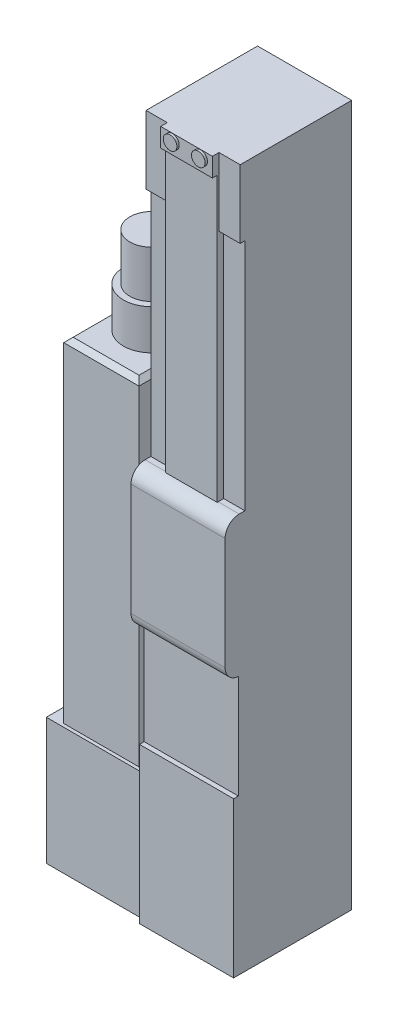
SolidWorks part; units mm, degrees
ref_plane "Front" through (0, 0, 0) normal (0, 0, 1) x (1, 0, 0)
ref_plane "Top" through (0, 0, 0) normal (0, 1, 0) x (1, 0, 0)
ref_plane "Right" through (0, 0, 0) normal (1, 0, 0) x (0, 0, -1)
sketch "Sketch1" plane through (0, 0, 0) normal (0, 0, 1) x (1, 0, 0)
  line L0 (0, 172.9723) -> (0, -36.0329) construction
  line L2 (10, 0) -> (-10, 0)
  line L3 (10, 0) -> (10, 149)
  line L4 (10, 149) -> (-10, 149)
  line L5 (-10, 0) -> (-10, 149)
  dimension "D1" = 149
  dimension "D2" = 20
extrude "Boss-Extrude1" add sketch "Sketch1" against normal blind 26.9
sketch "Sketch2" plane through (0, 0, 0) normal (0, -1, 0) x (1, 0, 0)
  line L0 (-10, -26.9) -> (-10, 0) construction
  line L1 (-31, -3) -> (-10, -3)
  line L2 (-31, -3) -> (-31, -20.5)
  line L3 (-31, -20.5) -> (-10, -20.5)
  line L4 (-10, -3) -> (-10, -20.5)
  line L6 (-10, 0) -> (10, 0) construction
  dimension "D1" = 3
  dimension "D2" = 17.5
  dimension "D3" = 31
extrude "Boss-Extrude2" add sketch "Sketch2" against normal blind 26.9
sketch "Sketch3" plane through (0, 26.9, 0) normal (0, 1, 0) x (1, 0, 0)
  line L1 (-28, 22.6) -> (-12, 22.6)
  line L2 (-28, 22.6) -> (-28, 3.7)
  line L3 (-28, 3.7) -> (-12, 3.7)
  line L4 (-12, 22.6) -> (-12, 3.7)
  line L5 (10, 0) -> (-10, 0) construction
  dimension "D1" = 18.9
  dimension "D2" = 3.7
  dimension "D3" = 12
  dimension "D4" = 16
extrude "Boss-Extrude3" add sketch "Sketch3" along normal blind 71.1
sketch "Sketch4" plane through (0, 98, 0) normal (0, 1, 0) x (1, 0, 0)
  line L1 (10, 0) -> (-10, 0) construction
  circle A0 centre (-20, 14.4) radius 6
  dimension "D1" = 12
  dimension "D2" = 14.4
  dimension "D3" = 20
extrude "Boss-Extrude4" add sketch "Sketch4" along normal blind 8.5
sketch "Sketch5" plane through (0, 106.5, 0) normal (0, 1, 0) x (1, 0, 0)
  circle A0 centre (-20, 14.4) radius 4.65
  dimension "D1" = 9.3
extrude "Boss-Extrude5" add sketch "Sketch5" along normal blind 10
sketch "Sketch7" plane through (0, 0, 0) normal (0, 0, 1) x (1, 0, 0)
  line L4 (10, 0) -> (10, 149)
  line L5 (10, 149) -> (-10, 149)
  line L6 (-10, 149) -> (-10, 0)
  line L7 (-10, 0) -> (10, 0)
  line L8 (10, 0) -> (10, 149)
  line L9 (10, 149) -> (-10, 149)
  line L10 (-10, 149) -> (-10, 0)
  line L11 (-10, 0) -> (10, 0)
  dimension "D1" = 0
extrude "Cut-Extrude1" cut sketch "Sketch7" against normal blind 2.8
sketch "Sketch8" plane through (0, 0, -2.8) normal (0, 0, 1) x (1, 0, 0)
  line L1 (-10, 149) -> (-5.5, 149)
  line L2 (-10, 149) -> (-10, 55)
  line L3 (-10, 55) -> (-5.5, 55)
  line L4 (-5.5, 149) -> (-5.5, 55)
  line L5 (-10, 0) -> (10, 0) construction
  line L6 (10, 149) -> (5.5, 149)
  line L7 (10, 149) -> (10, 55)
  line L8 (10, 55) -> (5.5, 55)
  line L9 (5.5, 149) -> (5.5, 55)
  dimension "D1" = 55
  dimension "D2" = 4.5
extrude "Cut-Extrude2" cut sketch "Sketch8" against normal blind 1.4
sketch "Sketch17" plane through (0, 0, -26.9) normal (0, 0, -1) x (-1, 0, 0)
  line L0 (0, 165.2015) -> (0, -12.9133) construction
  line L1 (0, 120) -> (0, 119) construction
  line L2 (1.5, 120) -> (1.5, 119)
  line L3 (-1.5, 120) -> (-1.5, 119)
  line L4 (10, 0) -> (-10, 0) construction
  arc A0 (1.5, 120) -> (-1.5, 120) centre (0, 120) ccw
  arc A1 (-1.5, 119) -> (1.5, 119) centre (0, 119) ccw
  circle A2 centre (0, 69.5) radius 1.5
  point P5 (0, 119.5)
  dimension "D3" = 3
  dimension "D1" = 1
  dimension "D2" = 3
  dimension "D4" = 69.5
  dimension "D5" = 50
extrude "Cut-Extrude3" cut sketch "Sketch17" against normal blind 3
sketch "Sketch9" plane through (0, 0, -4.2) normal (0, 0, 1) x (1, 0, 0)
  line L0 (10, 55) -> (10, 149) construction
  line L1 (-10, 55) -> (10, 55)
  line L2 (-10, 55) -> (-10, 84.8)
  line L3 (-10, 84.8) -> (10, 84.8)
  line L4 (10, 55) -> (10, 84.8)
  dimension "D1" = 29.8
extrude "Boss-Extrude6" add sketch "Sketch9" along normal blind 4.2
sketch "Sketch12" plane through (0, 0, -2.8) normal (0, 0, 1) x (1, 0, 0)
  line L0 (-10, 55) -> (-10, 0) construction
  line L1 (10, 0) -> (-10, 0)
  line L2 (10, 0) -> (10, 33)
  line L3 (10, 33) -> (-10, 33)
  line L4 (-10, 0) -> (-10, 33)
  dimension "D1" = 33
extrude "Boss-Extrude7" add sketch "Sketch12" along normal blind 1
sketch "Sketch14" plane through (0, 0, -2.8) normal (0, 0, 1) x (1, 0, 0)
  line L0 (5.5, 149) -> (5.5, 84.8) construction
  line L1 (-5.5, 149) -> (5.5, 149)
  line L2 (-5.5, 149) -> (-5.5, 145)
  line L3 (-5.5, 145) -> (5.5, 145)
  line L4 (5.5, 149) -> (5.5, 145)
  dimension "D1" = 4
extrude "Boss-Extrude8" add sketch "Sketch14" along normal blind 1
sketch "Sketch15" plane through (0, 0, -1.8) normal (0, 0, 1) x (1, 0, 0)
  line L0 (-10, 0) -> (10, 0) construction
  line L1 (0, 159.5543) -> (0, -7.81) construction
  circle A0 centre (-3, 147.5) radius 1.45
  circle A1 centre (3, 147.5) radius 1.45
  dimension "D1" = 2.9
  dimension "D2" = 147.5
  dimension "D3" = 6
extrude "Boss-Extrude9" add sketch "Sketch15" along normal blind 0.5
sketch "Sketch16" plane through (0, 0, -4.2) normal (0, 0, 1) x (1, 0, 0)
  line L0 (-5.5, 84.8) -> (-5.5, 145) construction
  line L1 (-10, 149) -> (-5.5, 149)
  line L2 (-10, 149) -> (-10, 134.5)
  line L3 (-10, 134.5) -> (-5.5, 134.5)
  line L4 (-5.5, 149) -> (-5.5, 134.5)
  line L5 (10, 84.8) -> (10, 149) construction
  line L6 (5.5, 149) -> (10, 149)
  line L7 (5.5, 149) -> (5.5, 134.5)
  line L8 (5.5, 134.5) -> (10, 134.5)
  line L9 (10, 149) -> (10, 134.5)
  dimension "D1" = 14.5
extrude "Boss-Extrude10" add sketch "Sketch16" along normal blind 1
hole_wizard "M3x0.5 Tapped Hole1" positions "Sketch11" profile "Sketch10" tap size "M3x0.5" standard "JIS"
sketch "Sketch11" plane through (0, 0, -26.9) normal (0, 0, -1) x (-1, 0, 0)
  line L0 (10, 0) -> (-10, 0) construction
  line L1 (0, 165.9273) -> (0, -22.1044) construction
  point P0 (-8, 69.5)
  point P1 (8, 69.5)
  dimension "D1" = 69.5
  dimension "D2" = 16
sketch "Sketch10" plane through (8, 69.5, -26.9) normal (1, 0, 0) x (0, 1, 0)
  line L0 (0, 0) -> (0, 6.2511)
  line L1 (0, 6.2511) -> (1.25, 5.5)
  line L2 (1.25, 5.5) -> (1.25, 0)
  line L5 (1.25, 0) -> (0, 0)
  line L10 (0, 6.2511) -> (-1.25, 5.5) construction
  line L11 (0, -6.35) -> (0, 107.95) construction
  dimension "Tap Drill Dia." = 2.5
  dimension "Tap Drill Depth" = 5.5
  dimension "Drill Angle" = 118
cosmetic thread "Hole Thread1" parameters "D1"=4, "D2"=3
cosmetic thread "Hole Thread2" parameters "D1"=4, "D2"=3
pattern_linear "LPattern1" count 3 spacing 25 along (0, 1, 0) of "M3x0.5 Tapped Hole1"
fillet "Fillet1" radius 3 2 edges at (0, 55, 0) (0, 84.8, 0)
chamfer "Chamfer1" distance 1 angle 45 4 edges at (-12, 98, -13.15) (-20, 98, -22.6) (-28, 98, -13.15) (-20, 98, -3.7)
